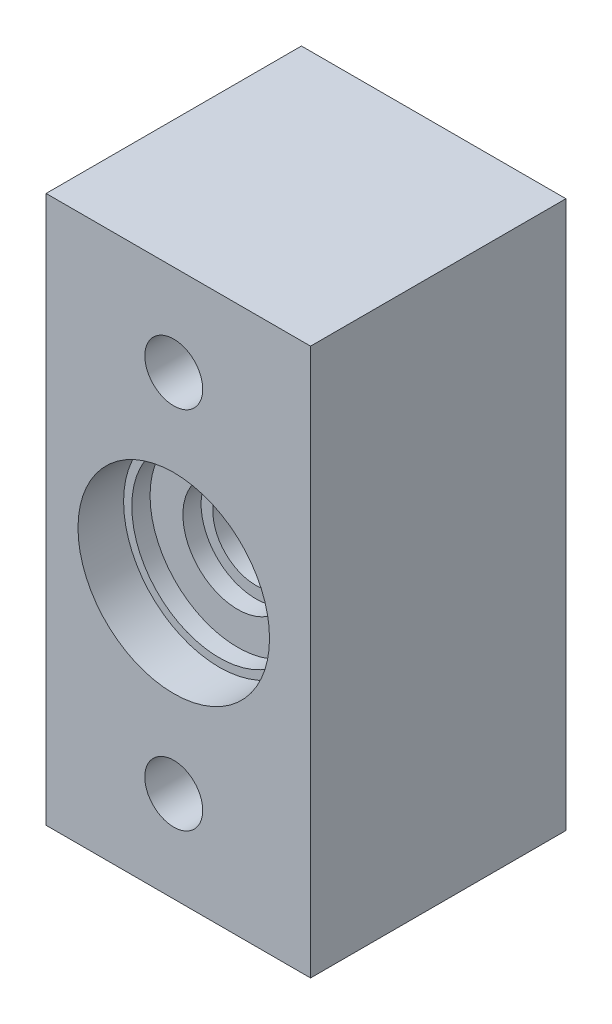
SolidWorks part; units mm, degrees
material "6061-T4 (SS)"
ref_plane "Front Plane" through (0, 0, 0) normal (0, 0, 1) x (1, 0, 0)
ref_plane "Top Plane" through (0, 0, 0) normal (0, 1, 0) x (1, 0, 0)
ref_plane "Right Plane" through (0, 0, 0) normal (1, 0, 0) x (0, 0, -1)
sketch "Sketch1" plane through (0, 0, 0) normal (0, 0, 1) x (1, 0, 0)
  line L5 (-6, 6) -> (0, 0) construction
  line L6 (0, 0) -> (6, 6) construction
  line L7 (7.5, 15) -> (-7.5, 15)
  line L8 (7.5, 15) -> (7.5, -15)
  line L9 (7.5, -15) -> (-7.5, -15)
  line L10 (-7.5, 15) -> (-7.5, -15)
  line L11 (7.5, 15) -> (-7.5, -15) construction
  line L12 (7.5, -15) -> (-7.5, 15) construction
  point P0 (0, 0)
  dimension "D1" = 15
  dimension "D4" = 30
extrude "Boss-Extrude1" add sketch "Sketch1" along normal blind 9
sketch "Sketch2" plane through (0, 0, 9) normal (0, 0, 1) x (1, 0, 0)
  circle A0 centre (0, 0) radius 5.25
  dimension "D1" = 10.5
extrude "Cut-Extrude1" cut sketch "Sketch2" against normal blind 2.5 contours A0
sketch "Sketch4" plane through (0, 0, 6.5) normal (0, 0, 1) x (1, 0, 0)
  circle A0 centre (0, 0) radius 4.8
  dimension "D1" = 9.6
extrude "Cut-Extrude3" cut sketch "Sketch4" against normal blind 1
sketch "Sketch5" plane through (0, 0, 5.5) normal (0, 0, 1) x (1, 0, 0)
  circle A0 centre (0, 0) radius 2.36
  dimension "D1" = 4.72
extrude "Cut-Extrude4" cut sketch "Sketch5" against normal blind 5 and the other way through all
sketch "Sketch6" plane through (0, 0, 0) normal (0, 0, 1) x (1, 0, 0)
  line L0 (-7, 15) -> (-7, -15)
  line L3 (7.5, 15) -> (-7.5, 15) construction
  line L4 (-7.5, -15) -> (7.5, -15) construction
  circle A0 centre (0, 0) radius 5.25 construction
  point P6 (-7, 0)
  dimension "D1" = 7
extrude "Cut-Extrude6" cut sketch "Sketch6" against normal through all and the other way through all flip side to cut
sketch "Sketch11" plane through (0, 0, 0) normal (0, 0, -1) x (-1, 0, 0)
  line L1 (7, 15) -> (-7.5, 15)
  line L2 (7, 15) -> (7, -15)
  line L3 (7, -15) -> (-7.5, -15)
  line L4 (-7.5, 15) -> (-7.5, -15)
extrude "Boss-Extrude5" add sketch "Sketch11" along normal blind 5
sketch "Sketch12" plane through (0, 0, -5) normal (0, 0, -1) x (-1, 0, 0)
  circle A0 centre (0, 0) radius 4
  dimension "D1" = 8
extrude "Cut-Extrude8" cut sketch "Sketch12" against normal blind 5
sketch "Sketch13" plane through (0, 0, -5) normal (0, 0, -1) x (-1, 0, 0)
  line L2 (7, 15) -> (-7.5, 15) construction
  line L3 (0, 15) -> (0, -15) construction
  line L4 (-7.5, -15) -> (7, -15) construction
  circle A1 centre (0, -10) radius 1.5875
  circle A2 centre (0, 10) radius 1.5875
  point P0 (0, 5)
  point P4 (0, -5)
  dimension "D3" = 3.175
  dimension "D1" = 5
  dimension "D2" = 5
extrude "Cut-Extrude9" cut sketch "Sketch13" against normal through all
sketch "Sketch14" plane through (0, 0, 5.5) normal (0, 0, 1) x (1, 0, 0)
  circle A0 centre (0, 0) radius 3
  dimension "D1" = 6
extrude "Cut-Extrude10" cut sketch "Sketch14" against normal blind 1
